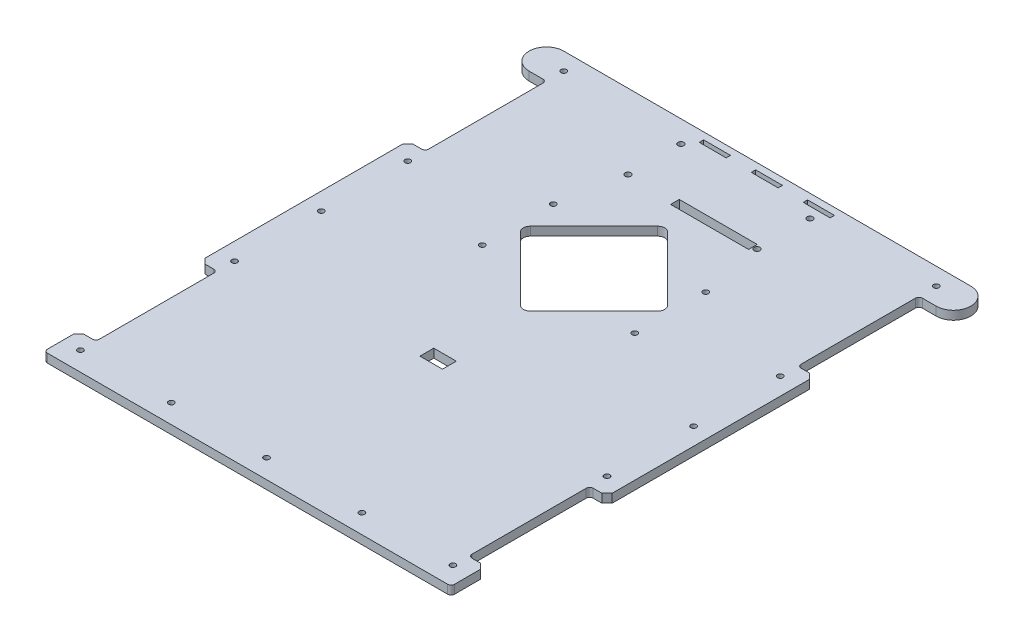
SolidWorks part; units mm, degrees
material "Teak"
ref_plane "Front Plane" through (0, 0, 0) normal (0, 0, 1) x (1, 0, 0)
ref_plane "Top Plane" through (0, 0, 0) normal (0, 1, 0) x (1, 0, 0)
ref_plane "Right Plane" through (0, 0, 0) normal (1, 0, 0) x (0, 0, -1)
sketch "Sketch1" plane through (0, 0, 0) normal (0, 1, 0) x (1, 0, 0)
  line L0 (0, 190) -> (0, -110) construction
  line L1 (-117.5, 0) -> (117.5, 0) construction
  line L2 (-117.5, -110) -> (117.5, -110)
  line L3 (117.5, -110) -> (117.5, -90)
  line L4 (117.5, -90) -> (107.5, -90)
  line L5 (107.5, -90) -> (107.5, -20)
  line L6 (107.5, -20) -> (117.5, -20)
  line L7 (117.5, -20) -> (117.5, 100)
  line L8 (117.5, 100) -> (107.5, 100)
  line L9 (107.5, 100) -> (107.5, 170)
  line L10 (107.5, 170) -> (127.5, 170)
  line L11 (-107.5, 170) -> (-127.5, 170)
  line L12 (-107.5, 100) -> (-107.5, 170)
  line L13 (-117.5, 100) -> (-107.5, 100)
  line L14 (-117.5, -20) -> (-117.5, 100)
  line L15 (-107.5, -20) -> (-117.5, -20)
  line L16 (-107.5, -90) -> (-107.5, -20)
  line L17 (-117.5, -90) -> (-107.5, -90)
  line L18 (-117.5, -110) -> (-117.5, -90)
  line L19 (127.5, 170) -> (127.5, 190)
  line L20 (127.5, 190) -> (-127.5, 190)
  line L21 (-127.5, 170) -> (-127.5, 190)
  point P5 (0, 0)
  dimension "D1" = 20
  dimension "D2" = 300
  dimension "D3" = 110
  dimension "D4" = 20
  dimension "D5" = 10
  dimension "D6" = 70
  dimension "D7" = 70
  dimension "D8" = 255
  dimension "D9" = 20
extrude "Boss-Extrude1" add sketch "Sketch1" along normal blind 5
fillet "Fillet3" 2 edges at (127.5, 2.5, -170) (127.5, 2.5, -190) type full round first side face at (117.5, 2.5, -170) second side face at (0, 2.5, -190) middle face at (127.5, 2.5, -180)
fillet "Fillet4" 2 edges at (-127.5, 2.5, -190) (-127.5, 2.5, -170) type full round first side face at (-5, 2.5, -190) second side face at (-117.5, 2.5, -170) middle face at (-127.5, 2.5, -180)
fillet "Fillet2" radius 2 10 edges at (107.5, 2.5, 20) (107.5, 2.5, -170) (107.5, 2.5, -100) (107.5, 2.5, 90) (-107.5, 2.5, -100) (-107.5, 2.5, 90) (-107.5, 2.5, 20) (-107.5, 2.5, -170) (-117.5, 2.5, 110) (117.5, 2.5, 110)
sketch "Sketch2" plane through (0, 5, 0) normal (0, 1, 0) x (1, 0, 0)
  line L0 (0, -110) -> (0, 90) construction
  line L1 (-115.5, -110) -> (115.5, -110) construction
  line L2 (107.5, 102) -> (107.5, 168) construction
  line L4 (117.5, -20) -> (117.5, 100) construction
  line L5 (117.5, -108) -> (117.5, -90) construction
  arc A0 (117.5, 170) -> (117.5, 190) centre (117.5, 180) ccw construction
  circle A1 centre (107.5, 180) radius 1.6
  circle A2 centre (107.5, 40) radius 1.6
  circle A3 centre (107.5, -99) radius 1.6
  circle A4 centre (-107.5, 40) radius 1.6
  circle A5 centre (-107.5, -99) radius 1.6
  circle A6 centre (-107.5, 40) radius 1.6
  circle A7 centre (-107.5, 180) radius 1.6
  circle A8 centre (107.5, 40) radius 1.6
  circle A9 centre (-107.5, 40) radius 1.6
  circle A10 centre (107.5, 40) radius 1.6
  circle A11 centre (0, -99) radius 1.6
  circle A12 centre (55, -99) radius 1.6
  circle A13 centre (-55, -99) radius 1.6
  circle A14 centre (-107.5, 90) radius 1.6
  circle A15 centre (107.5, 90) radius 1.6
  circle A16 centre (-107.5, -10) radius 1.6
  circle A17 centre (107.5, -10) radius 1.6
  point P17 (127.5, 180)
  point P26 (117.5, 40)
  point P30 (117.5, -99)
  dimension "D1" = 3.2
  dimension "D2" = 2
  dimension "D3" = 10
  dimension "D4" = 2
  dimension "D5" = 2
  dimension "D6" = 2
  dimension "D7" = 2
  dimension "D8" = 2
extrude "layer fix hole" cut sketch "Sketch2" against normal through all both and the other way through all contours A13 | A5 | A11 | A12 | A3 | A2 | A4 | A7 | A1 | A16 | A14 | A17 | A15
sketch "Sketch3" plane through (0, 5, 0) normal (0, 1, 0) x (1, 0, 0)
  line L0 (0, 190) -> (0, -110) construction
  line L1 (117.5, 190) -> (-117.5, 190) construction
  line L2 (-115.5, -110) -> (115.5, -110) construction
  line L3 (-39.598, 92.8284) -> (-2.8284, 129.598)
  line L8 (-50, 116.5) -> (50, 116.5) construction
  line L9 (-50, 116.5) -> (-50, 63.5) construction
  line L14 (-50, 63.5) -> (50, 63.5) construction
  line L15 (50, 116.5) -> (50, 63.5) construction
  line L21 (-50, 116.5) -> (50, 63.5) construction
  line L22 (-50, 63.5) -> (50, 116.5) construction
  line L23 (-39.598, 87.1716) -> (-2.8284, 50.402)
  line L24 (2.8284, 129.598) -> (39.598, 92.8284)
  line L25 (2.8284, 50.402) -> (39.598, 87.1716)
  line L26 (-35.0018, 90) -> (39.9515, 90) construction
  line L27 (0, 127.4767) -> (0, 52.5233) construction
  circle A12 centre (44, 110.5) radius 1.6
  circle A13 centre (44, 69.5) radius 1.6
  circle A14 centre (-44, 69.5) radius 1.6
  circle A15 centre (-44, 110.5) radius 1.6
  arc A16 (-2.8284, 129.598) -> (2.8284, 129.598) centre (0, 126.7696) cw
  arc A17 (39.598, 92.8284) -> (39.598, 87.1716) centre (36.7696, 90) cw
  arc A18 (-2.8284, 50.402) -> (2.8284, 50.402) centre (0, 53.2304) ccw
  arc A19 (-39.598, 87.1716) -> (-39.598, 92.8284) centre (-36.7696, 90) cw
  point P6 (0, 90)
  point P20 (0, 90)
  point P21 (-21.2132, 111.2132)
  point P22 (21.2132, 68.7868)
  dimension "D3" = 3.2
  dimension "D2" = 100
  dimension "D9" = 6
  dimension "D14" = 4
  dimension "D1" = 53
  dimension "D4" = 6
  dimension "D5" = 6
  dimension "D6" = 6
  dimension "D7" = 6
  dimension "D8" = 6
  dimension "D10" = 6
  dimension "D11" = 6
  dimension "D12" = 60
  dimension "D13" = 100
extrude "arm fix hole" cut sketch "Sketch3" against normal through all
sketch "Sketch4" plane through (0, 5, 0) normal (0, 1, 0) x (1, 0, 0)
  line L0 (0, 0) -> (0, 190) construction
  line L1 (117.5, 190) -> (-117.5, 190) construction
  line L2 (-32.75, 186) -> (-32.75, 183.5)
  line L3 (-72.75, 186) -> (-57.25, 186)
  line L4 (-72.75, 186) -> (-72.75, 183.5)
  line L5 (-72.75, 183.5) -> (-57.25, 183.5)
  line L6 (-57.25, 186) -> (-57.25, 183.5)
  line L7 (-17.25, 183.5) -> (-32.75, 183.5)
  line L8 (-17.25, 186) -> (-17.25, 183.5)
  line L9 (-17.25, 186) -> (-32.75, 186)
  line L10 (5, 97.0905) -> (5, 68.2589) construction
  line L11 (-85, 183.5) -> (85, 183.5) construction
  line L12 (-85, 183.5) -> (-85, 186) construction
  line L13 (-85, 186) -> (85, 186) construction
  line L14 (85, 183.5) -> (85, 186) construction
  line L15 (-25, 68.2589) -> (-25, 97.0905) construction
  line L16 (-65, 97.0905) -> (-65, 68.2589) construction
  line L17 (-25, 68.2589) -> (-25, 97.0905) construction
  line L18 (35, 68.2589) -> (35, 97.0905) construction
  line L20 (-2.75, 183.5) -> (12.75, 183.5)
  line L21 (-2.75, 183.5) -> (-2.75, 186)
  line L22 (-2.75, 186) -> (12.75, 186)
  line L23 (12.75, 183.5) -> (12.75, 186)
  line L24 (27.25, 183.5) -> (42.75, 183.5)
  line L25 (27.25, 183.5) -> (27.25, 186)
  line L26 (27.25, 186) -> (42.75, 186)
  line L27 (42.75, 183.5) -> (42.75, 186)
  point P17 (-65, 183.5)
  point P25 (-25, 183.5)
  point P35 (5, 186)
  point P36 (35, 186)
  dimension "D1" = 15.5
  dimension "D2" = 2.5
  dimension "D3" = 4
  dimension "D4" = 20
  dimension "D5" = 170
  dimension "D6" = 60
  dimension "D7" = 90
  dimension "D8" = 120
extrude "IR fix hole" cut sketch "Sketch4" against normal through all
chamfer "Chamfer1" distance 3 angle 45 6 edges at (117.5, 2.5, 20) (-117.5, 2.5, -100) (-117.5, 2.5, 20) (-117.5, 2.5, 90) (117.5, 2.5, -100) (117.5, 2.5, 90)
sketch "Sketch5" plane through (0, 5, 0) normal (0, 1, 0) x (1, 0, 0)
  line L1 (-57.25, 183.5) -> (-72.75, 183.5)
  line L2 (-57.25, 183.5) -> (-57.25, 186)
  line L3 (-57.25, 186) -> (-72.75, 186)
  line L4 (-72.75, 183.5) -> (-72.75, 186)
extrude "Boss-Extrude2" add sketch "Sketch5" against normal up to surface (5 mm away) up to face at (-65, 0, -184.75)
sketch "Sketch6" plane through (0, 5, 0) normal (0, 1, 0) x (1, 0, 0)
  line L0 (0, 110) -> (0, -110) construction
  line L1 (-115.5, -110) -> (115.5, -110) construction
  line L3 (6.5, -4) -> (-6.5, -4)
  line L4 (6.5, -4) -> (6.5, 4)
  line L5 (6.5, 4) -> (-6.5, 4)
  line L6 (-6.5, -4) -> (-6.5, 4)
  line L7 (6.5, -4) -> (-6.5, 4) construction
  line L8 (6.5, 4) -> (-6.5, -4) construction
  point P0 (0, 0)
  point P6 (0, 0)
  dimension "D1" = 13
  dimension "D2" = 8
extrude "Turn on/off Switch " cut sketch "Sketch6" against normal up to next
ref_plane "Plane1" through (0, 0, 0) normal (-1, 0, 0) x (0, 0, 1)
sketch "Sketch9" plane through (0, 5, 0) normal (0, 1, 0) x (1, 0, 0)
  line L0 (-10, 144.2) -> (-10, 149.2)
  line L1 (40, 180) -> (-40, 180) construction
  line L148 (-10, 149.2) -> (35, 149.2)
  line L149 (35, 149.2) -> (35, 144.2)
  line L150 (35, 144.2) -> (40, 144.2) construction
  line L249 (-40, 144.2) -> (-10, 144.2) construction
  line L250 (40, 144.2) -> (40, 180) construction
  line L251 (-40, 180) -> (-40, 144.2) construction
  line L252 (0, 190) -> (0, -110) construction
  line L253 (0, 190) -> (0, -110) construction
  line L254 (-40, 162.1) -> (40, 162.1) construction
  line L255 (-10, 144.2) -> (35, 144.2)
  line L257 (127.5, 190) -> (-127.5, 190) construction
  circle A40 centre (-37.25, 177.35) radius 1.7
  circle A42 centre (37.25, 177.35) radius 1.7
  circle A43 centre (37.25, 146.85) radius 1.7
  circle A44 centre (-37.25, 146.85) radius 1.7
  point P2 (-18.9939, 167.9565)
  point P9 (0, 180)
  dimension "D4" = 2.65
  dimension "D2" = 35.8
  dimension "D13" = 3.4
  dimension "D3" = 80
  dimension "D8" = 5
  dimension "D9" = 5
  dimension "D10" = 45
  dimension "D11" = 10
  dimension "D12" = 2.75
extrude "Cut-Extrude2" cut sketch "Sketch9" against normal through all both
